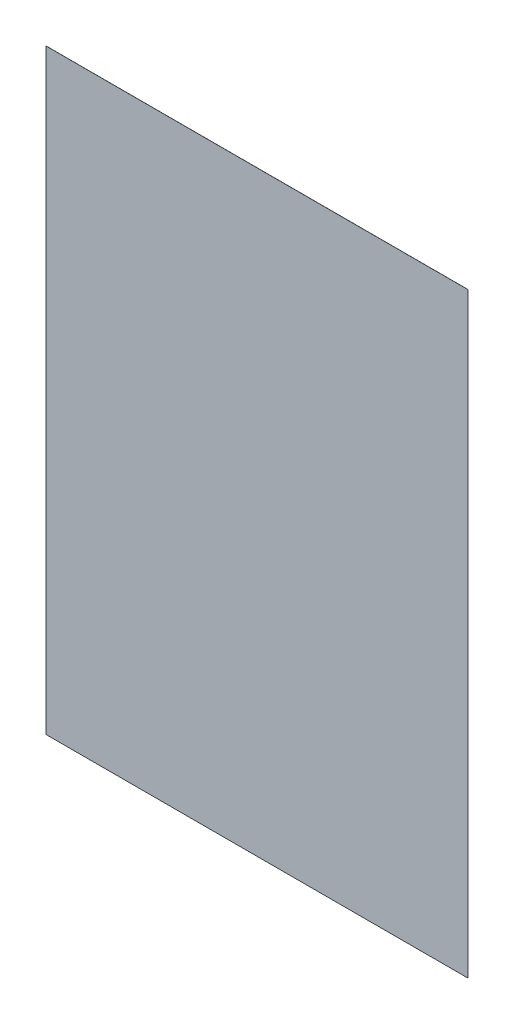
SolidWorks part; units mm, degrees
ref_plane "Front Plane" through (0, 0, 0) normal (0, 0, 1) x (1, 0, 0)
ref_plane "Top Plane" through (0, 0, 0) normal (0, 1, 0) x (1, 0, 0)
ref_plane "Right Plane" through (0, 0, 0) normal (1, 0, 0) x (0, 0, -1)
sketch "Sketch1" plane through (0, 0, 0) normal (0, 0, 1) x (1, 0, 0)
  line L0 (-105, 148.5) -> (105, -148.5) construction
  line L1 (-105, 148.5) -> (105, 148.5)
  line L2 (-105, 148.5) -> (-105, -148.5)
  line L3 (-105, -148.5) -> (105, -148.5)
  line L4 (105, 148.5) -> (105, -148.5)
  dimension "D1" = 297
  dimension "D2" = 210
extrude "Boss-Extrude1" add sketch "Sketch1" along normal blind 0.05
